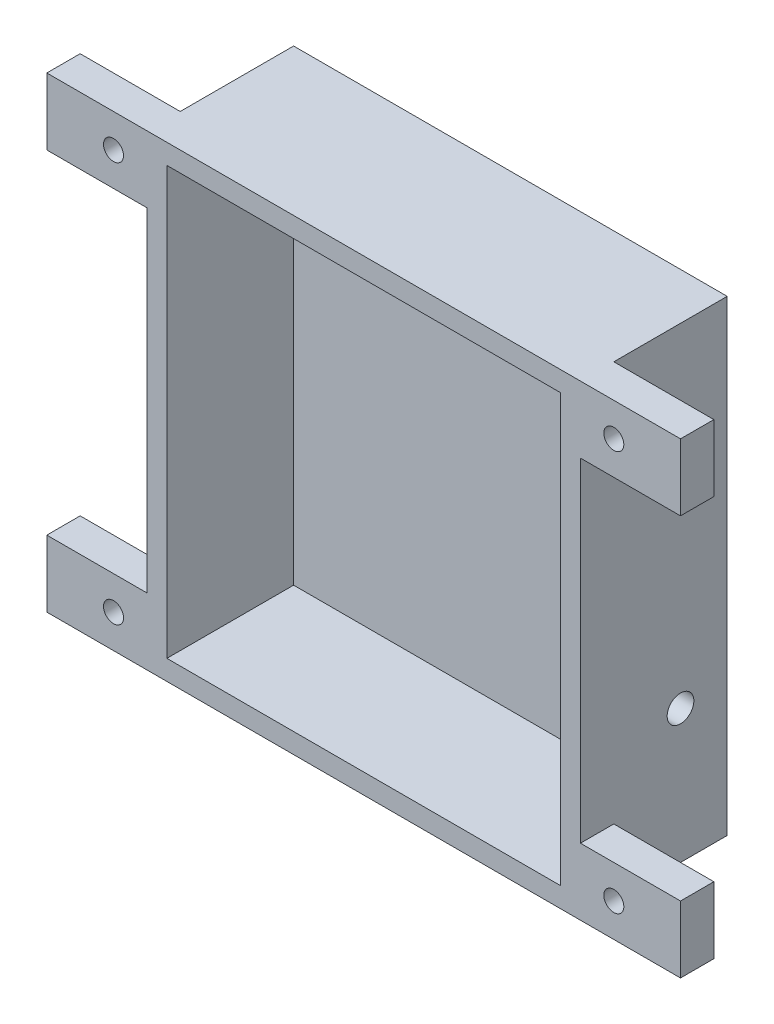
SolidWorks part; units mm, degrees
material "ABS"
ref_plane "Front Plane" through (0, 0, 0) normal (0, 0, 1) x (1, 0, 0)
ref_plane "Top Plane" through (0, 0, 0) normal (0, 1, 0) x (1, 0, 0)
ref_plane "Right Plane" through (0, 0, 0) normal (1, 0, 0) x (0, 0, -1)
sketch "Sketch1" plane through (0, 0, 0) normal (0, 0, 1) x (1, 0, 0)
  line L1 (0, 0) -> (59, 0)
  line L2 (0, 0) -> (0, 64)
  line L3 (0, 64) -> (59, 64)
  line L4 (59, 0) -> (59, 64)
  dimension "D1" = 64
  dimension "D2" = 59
extrude "Boss-Extrude1" add sketch "Sketch1" along normal blind 19
shell "Shell1" thickness 3 removed face at (29.5, 32, 19) outward yes
sketch "Sketch2" plane through (62, 0, 0) normal (1, 0, 0) x (0, 0, -1)
  line L3 (-19, -3) -> (-19, 67) construction
  circle A0 centre (-4, 17) radius 2
  dimension "D1" = 4
  dimension "D3" = 17
  dimension "D2" = 15
extrude "Cut-Extrude1" cut sketch "Sketch2" against normal blind 19
ref_plane "Plane1" through (0, 32, 0) normal (0, 1, 0) x (1, 0, 0)
sketch "Sketch3" plane through (62, 0, 0) normal (1, 0, 0) x (0, 0, -1)
  line L1 (-19, 67) -> (-14, 67)
  line L2 (-19, 67) -> (-19, 57)
  line L3 (-19, 57) -> (-14, 57)
  line L4 (-14, 67) -> (-14, 57)
  line L5 (-19, -3) -> (-14, -3)
  line L6 (-19, -3) -> (-19, 7)
  line L7 (-19, 7) -> (-14, 7)
  line L8 (-14, -3) -> (-14, 7)
  dimension "D1" = 5
  dimension "D2" = 10
  dimension "D3" = 10
  dimension "D4" = 5
extrude "Boss-Extrude2" add sketch "Sketch3" along normal blind 15
sketch "Sketch4" plane through (-3, 0, 0) normal (-1, 0, 0) x (0, 0, 1)
  line L1 (19, -3) -> (14, -3)
  line L2 (19, -3) -> (19, 7)
  line L3 (19, 7) -> (14, 7)
  line L4 (14, -3) -> (14, 7)
  line L5 (19, 67) -> (14, 67)
  line L6 (19, 67) -> (19, 57)
  line L7 (19, 57) -> (14, 57)
  line L8 (14, 67) -> (14, 57)
  dimension "D1" = 5
  dimension "D2" = 10
  dimension "D3" = 5
  dimension "D4" = 10
extrude "Boss-Extrude3" add sketch "Sketch4" along normal blind 15
sketch "Sketch5" plane through (0, 0, 14) normal (0, 0, -1) x (-1, 0, 0)
  line L1 (-77, 57) -> (-77, 67) construction
  line L3 (18, 7) -> (18, -3) construction
  line L4 (-62, 57) -> (-62, 67) construction
  line L5 (3, 67) -> (3, -3) construction
  circle A0 centre (-67, 62) radius 1.5
  circle A1 centre (8, 2) radius 1.5
  circle A2 centre (-67, 2) radius 1.5
  circle A3 centre (8, 62) radius 1.5
  point P8 (-77, 62)
  point P16 (18, 2)
  point P20 (0, 0)
  point P21 (0, 0)
  point P22 (0, 0)
  point P23 (0, 0)
  point P24 (0, 0)
  dimension "D1" = 3
  dimension "D2" = 3
  dimension "D3" = 3
  dimension "D4" = 3
  dimension "D5" = 5
  dimension "D6" = 5
extrude "Cut-Extrude2" cut sketch "Sketch5" against normal blind 10
